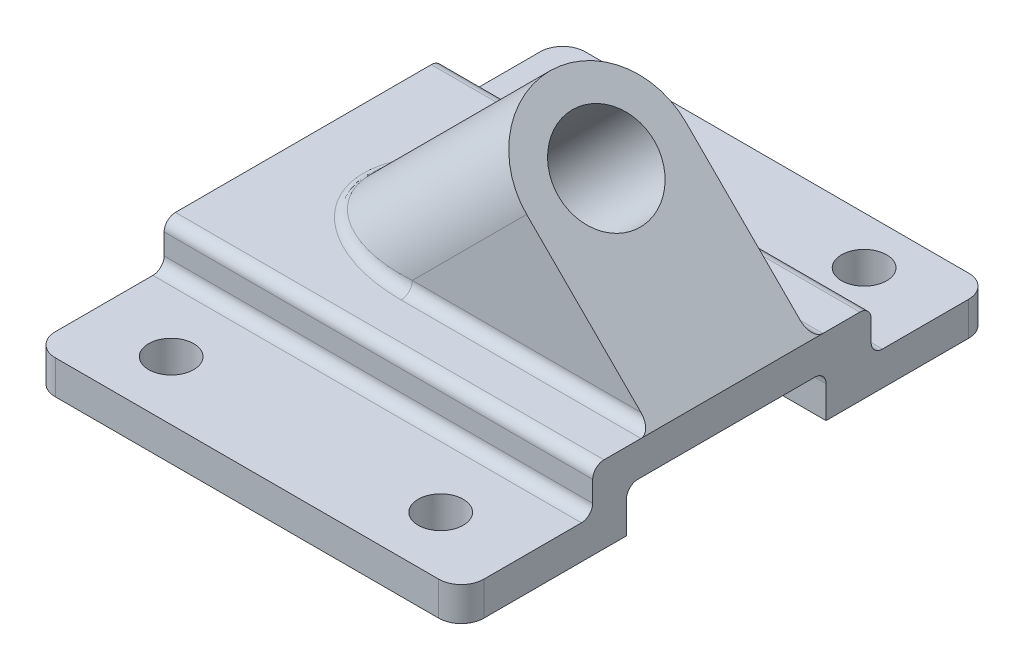
SolidWorks part; units mm, degrees
ref_plane "Front Plane" through (0, 0, 0) normal (0, 0, 1) x (1, 0, 0)
ref_plane "Top Plane" through (0, 0, 0) normal (0, 1, 0) x (1, 0, 0)
ref_plane "Right Plane" through (0, 0, 0) normal (1, 0, 0) x (0, 0, -1)
sketch "Sketch9" plane through (0, 0, 0) normal (1, 0, 0) x (0, 0, -1)
  line L0 (10.005, 0) -> (56.5219, 0)
  line L1 (56.5219, 0) -> (56.5219, 9.0116)
  line L2 (59.6969, 12.1866) -> (109.5164, 12.1866)
  line L3 (10.005, 9.525) -> (43.8219, 9.525)
  line L4 (46.9969, 12.7) -> (46.9969, 18.5366)
  line L5 (50.1719, 21.7116) -> (122.2164, 21.7116)
  line L6 (46.9969, 21.7116) -> (96.2968, 21.7116) construction
  line L7 (46.9969, 9.525) -> (46.9969, 21.7116) construction
  line L8 (0, 9.525) -> (46.9969, 9.525) construction
  line L9 (125.3914, 12.7) -> (125.3914, 18.5366)
  line L10 (159.2084, 9.525) -> (128.5664, 9.525)
  line L11 (112.6914, 0) -> (112.6914, 9.0116)
  line L12 (159.2084, 0) -> (112.6914, 0)
  line L13 (10.005, 9.525) -> (10.005, 0)
  line L14 (159.2084, 9.525) -> (159.2084, 0)
  line L15 (56.5219, 0) -> (56.5219, 12.1866) construction
  line L17 (0, 0) -> (56.5219, 0) construction
  line L18 (56.5219, 12.1866) -> (96.2968, 12.1866) construction
  arc A0 (50.1719, 21.7116) -> (46.9969, 18.5366) centre (50.1719, 18.5366) ccw
  arc A1 (46.9969, 12.7) -> (43.8219, 9.525) centre (43.8219, 12.7) cw
  arc A2 (125.3914, 12.7) -> (128.5664, 9.525) centre (128.5664, 12.7) ccw
  arc A3 (122.2164, 21.7116) -> (125.3914, 18.5366) centre (122.2164, 18.5366) cw
  arc A4 (59.6969, 12.1866) -> (56.5219, 9.0116) centre (59.6969, 9.0116) ccw
  arc A5 (109.5164, 12.1866) -> (112.6914, 9.0116) centre (109.5164, 9.0116) cw
  point P21 (86.1942, 21.7116)
  point P25 (84.6067, 12.1866)
  dimension "D2" = 3.175
  dimension "D3" = 3.175
  dimension "D1" = 9.525
extrude "Extrude5" add sketch "Sketch9" against normal blind 120.65
fillet "Fillet1" radius 6.35 4 edges at (-120.65, 4.7625, -159.2084) (0, 4.7625, -159.2084) (-120.65, 4.7625, -10.005) (0, 4.7625, -10.005)
ref_plane "Plane3" through (10.8558, 10.8558, 0) normal (0.7071, 0.7071, 0) x (0, 0, -1)
sketch "Sketch10" plane through (10.8558, 10.8558, 0) normal (0.7071, 0.7071, 0) x (0, 0, -1)
  line L1 (122.2164, 15.3524) -> (50.1719, 15.3524) construction
  line L2 (108.6293, 65.3527) -> (108.6293, 15.3524)
  line L3 (63.7591, 65.3527) -> (63.7591, 15.3524)
  line L4 (63.7591, 15.3524) -> (108.6293, 15.3524)
  arc A0 (108.6293, 65.3527) -> (63.7591, 65.3527) centre (86.1942, 65.3527) ccw
  circle A1 centre (86.1942, 65.3527) radius 13.5097
extrude "Extrude6" add sketch "Sketch10" against normal up to body separate body
sketch "Sketch11" plane through (10.8558, 10.8558, 0) normal (0.7071, 0.7071, 0) x (0, 0, -1)
  circle A0 centre (86.1942, 65.3527) radius 13.5097 construction
  circle A1 centre (86.1942, 65.3527) radius 13.5097
extrude "Extrude7" cut sketch "Sketch11" against normal blind 114.3
fillet "Fillet2" radius 3.175 3 edges at (-35.3555, 21.7116, -108.6293) (-102.439, 21.7116, -86.1942) (-35.3555, 21.7116, -63.7591)
ref_plane "Plane4" through (0, 9.525, 0) normal (0, 1, 0) x (-1, 0, 0)
sketch "Sketch12" plane through (0, 9.525, 0) normal (0, 1, 0) x (-1, 0, 0)
  line L0 (0, -26.5905) -> (22.3895, -26.5905) construction
  line L1 (0, -43.8219) -> (0, -16.355) construction
  line L2 (60.325, -10.005) -> (60.325, -43.8219) construction
  line L3 (114.3, -10.005) -> (6.35, -10.005) construction
  line L4 (120.65, -43.8219) -> (0, -43.8219) construction
  line L5 (0, -86.1942) -> (143.7584, -86.1942) construction
  line L6 (0, -60.5841) -> (0, -111.8043) construction
  circle A0 centre (22.3895, -26.5905) radius 6.35
  circle A1 centre (98.2605, -26.5905) radius 6.35
  circle A2 centre (98.2605, -145.7978) radius 6.35
  circle A3 centre (22.3895, -145.7978) radius 6.35
extrude "Extrude8" cut sketch "Sketch12" against normal blind 114.3
